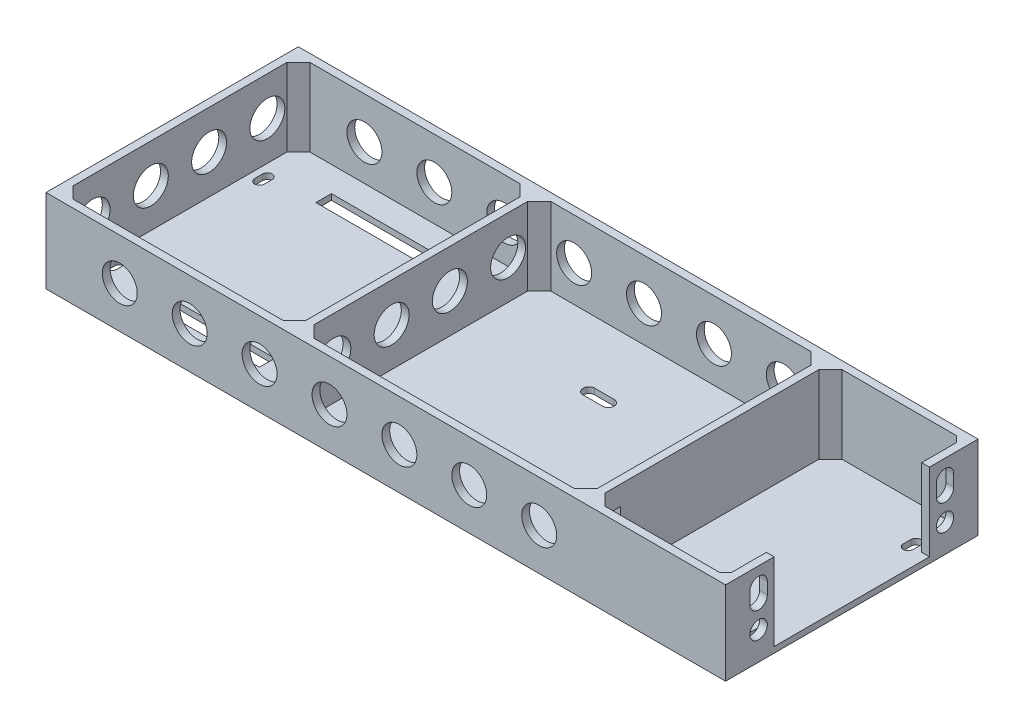
SolidWorks part; units mm, degrees
ref_plane "Спереди" through (0, 0, 0) normal (0, 0, 1) x (1, 0, 0)
ref_plane "Сверху" through (0, 0, 0) normal (0, 1, 0) x (1, 0, 0)
ref_plane "Справа" through (0, 0, 0) normal (1, 0, 0) x (0, 0, -1)
sketch "Эскиз1" plane through (0, 0, 0) normal (0, 1, 0) x (1, 0, 0)
  line L1 (-87.5, -32.5) -> (87.5, -32.5)
  line L2 (-87.5, -32.5) -> (-87.5, 32.5)
  line L3 (-87.5, 32.5) -> (87.5, 32.5)
  line L4 (87.5, -32.5) -> (87.5, 32.5)
  line L5 (-87.5, -32.5) -> (87.5, 32.5) construction
  line L6 (-87.5, 32.5) -> (87.5, -32.5) construction
  point P0 (0, 0)
  dimension "D1" = 175
  dimension "D2" = 65
extrude "Бобышка-Вытянуть1" add sketch "Эскиз1" along normal blind 1.5
sketch "Эскиз3" plane through (0, 1.5, 0) normal (0, 1, 0) x (1, 0, 0)
  line L5 (-87.5, -32.5) -> (87.5, -32.5)
  line L6 (-87.5, -32.5) -> (-87.5, 32.5)
  line L7 (-87.5, 32.5) -> (87.5, 32.5)
  line L8 (85.5, -30.5) -> (85.5, 30.5)
  line L9 (85.5, 30.5) -> (-85.5, 30.5)
  line L10 (-85.5, 30.5) -> (-85.5, -30.5)
  line L11 (-85.5, -30.5) -> (85.5, -30.5)
  line L12 (85.5, -30.5) -> (85.5, 30.5)
  line L13 (85.5, 30.5) -> (-85.5, 30.5)
  line L14 (-85.5, 30.5) -> (-85.5, -30.5)
  line L15 (-85.5, -30.5) -> (85.5, -30.5)
  line L16 (87.5, -32.5) -> (87.5, 32.5)
  line L17 (-87.5, -32.5) -> (87.5, 32.5) construction
  line L18 (-87.5, 32.5) -> (87.5, -32.5) construction
  point P0 (0, 0)
  dimension "D1" = 2
extrude "Бобышка-Вытянуть2" add sketch "Эскиз3" along normal blind 20
sketch "Эскиз4" plane through (87.5, 0, 0) normal (1, 0, 0) x (0, 0, -1)
  line L7 (-32.5, 21.5) -> (32.5, 21.5) construction
  line L8 (-20, 21.5) -> (20, 21.5)
  line L9 (-20, 21.5) -> (-20, 1.5)
  line L10 (-20, 1.5) -> (20, 1.5)
  line L11 (20, 21.5) -> (20, 1.5)
  line L12 (-32.5, 21.5) -> (-32.5, 0) construction
  dimension "D1" = 40
  dimension "D2" = 20
  dimension "D3" = 12.5
extrude "Вырез-Вытянуть1" cut sketch "Эскиз4" against normal blind 2
sketch "Эскиз5" plane through (0, 1.5, 0) normal (0, 1, 0) x (1, 0, 0)
  line L0 (57.5, 20) -> (57.5, 30.5)
  line L1 (87.5, 20) -> (57.5, 20)
  line L2 (87.5, 20) -> (87.5, -20)
  line L3 (87.5, -20) -> (57.5, -20)
  line L4 (57.5, 20) -> (57.5, -20)
  line L5 (85.5, 30.5) -> (-85.5, 30.5) construction
  line L6 (57.5, -20) -> (57.5, -30.5)
  line L7 (-85.5, -30.5) -> (85.5, -30.5) construction
  dimension "D1" = 30
  dimension "D2" = 40
sketch "Эскиз6" plane through (87.5, 0, 0) normal (1, 0, 0) x (0, 0, -1)
  line L0 (-32.5, 21.5) -> (-20, 21.5) construction
  line L1 (-20, 21.5) -> (-20, 1.5) construction
  line L2 (-24, 16.9184) -> (-24, 13.9184) construction
  line L3 (-21.75, 16.9184) -> (-21.75, 13.9184)
  line L4 (-26.25, 16.9184) -> (-26.25, 13.9184)
  circle A1 centre (-24, 7.25) radius 2.25
  arc A2 (-21.75, 16.9184) -> (-26.25, 16.9184) centre (-24, 16.9184) ccw
  arc A3 (-26.25, 13.9184) -> (-21.75, 13.9184) centre (-24, 13.9184) ccw
  point P8 (-24, 15.4184)
  dimension "D1" = 4.5
  dimension "D3" = 4.5
  dimension "D2" = 3
  dimension "D4" = 14.25
  dimension "D6" = 4
extrude "Вырез-Вытянуть2" cut sketch "Эскиз6" against normal blind 2
ref_plane "Плоскость2" through (0, 0, 0) normal (0, 0, -1) x (-1, 0, 0)
mirror "Зеркальное отражение2" about plane through (0, 0, 0) normal (0, 0, -1) of "Вырез-Вытянуть2"
sketch "Эскиз9" plane through (0, 1.5, 0) normal (0, 1, 0) x (1, 0, 0)
  line L0 (85.5, 20) -> (85.5, 30.5) construction
  line L1 (49.5, 30.5) -> (51.5, 30.5)
  line L2 (49.5, 30.5) -> (49.5, -30.5)
  line L3 (49.5, -30.5) -> (51.5, -30.5)
  line L4 (51.5, 30.5) -> (51.5, -30.5)
  line L5 (85.5, 30.5) -> (-85.5, 30.5) construction
  line L6 (-85.5, -30.5) -> (85.5, -30.5) construction
  dimension "D1" = 2
  dimension "D2" = 34
  dimension "D3" = 0
  dimension "D4" = 0
extrude "Бобышка-Вытянуть4" add sketch "Эскиз9" along normal blind 20
sketch "Эскиз12" plane through (51.5, 0, 0) normal (1, 0, 0) x (0, 0, -1)
  line L0 (-30.5, 21.5) -> (30.5, 21.5) construction
  line L1 (-27.5, 16.5) -> (-23.5, 16.5)
  line L2 (-27.5, 16.5) -> (-27.5, 6.5)
  line L3 (-27.5, 6.5) -> (-23.5, 6.5)
  line L4 (-23.5, 16.5) -> (-23.5, 6.5)
  line L5 (-30.5, 21.5) -> (-30.5, 1.5) construction
  dimension "D1" = 10
  dimension "D2" = 4
  dimension "D3" = 5
  dimension "D4" = 3
extrude "Вырез-Вытянуть4" cut sketch "Эскиз12" against normal blind 2
chamfer "Фаска1" distance 3 angle 45 4 edges at (-85.5, 11.5, -30.5) (49.5, 11.5, 30.5) (49.5, 11.5, -30.5) (-85.5, 11.5, 30.5)
chamfer "Фаска2" distance 3 angle 45 2 edges at (51.5, 11.5, -30.5) (51.5, 11.5, 30.5)
chamfer "Фаска3" distance 1.5 angle 45 2 edges at (85.5, 11.5, 30.5) (85.5, 11.5, -30.5)
sketch "Эскиз13" plane through (0, 0, -32.5) normal (0, 0, -1) x (-1, 0, 0)
  line L21 (-87.5, 10.75) -> (86.3564, 10.75) construction
  line L22 (-87.5, 21.5) -> (-87.5, 0) construction
  line L23 (-49.5, 16.5) -> (-49.5, 21.5) construction
  circle A0 centre (-39.5, 10.75) radius 4.5
  dimension "D2" = 9
  dimension "D1" = 10
extrude "Вырез-Вытянуть5" cut sketch "Эскиз13" against normal blind 71
ref_plane "Плоскость3" through (39.5, 0, 0) normal (-1, 0, 0) x (0, 0, 1)
pattern_linear "Линейный массив1" count 7 spacing 18 along (-1, 0, 0) of "Вырез-Вытянуть5"
sketch "Эскиз14" plane through (0, 1.5, 0) normal (0, 1, 0) x (1, 0, 0)
  line L0 (-85.5, 27.5) -> (-85.5, -27.5) construction
  line L1 (-25.5, 30.5) -> (-23.5, 30.5)
  line L2 (-25.5, 30.5) -> (-25.5, -30.5)
  line L3 (-25.5, -30.5) -> (-23.5, -30.5)
  line L4 (-23.5, 30.5) -> (-23.5, -30.5)
  line L5 (46.5, 30.5) -> (-82.5, 30.5) construction
  line L6 (-82.5, -30.5) -> (46.5, -30.5) construction
  point P6 (-24.5, 30.5)
  dimension "D1" = 60
  dimension "D2" = 0
  dimension "D3" = 0
  dimension "D4" = 2
extrude "Бобышка-Вытянуть5" add sketch "Эскиз14" along normal blind 20
chamfer "Фаска4" distance 3 angle 45 2 edges at (-25.5, 11.5, 30.5) (-25.5, 11.5, -30.5)
chamfer "Фаска5" distance 3 angle 45 2 edges at (-23.5, 11.5, 30.5) (-23.5, 11.5, -30.5)
sketch "Эскиз15" plane through (-23.5, 0, 0) normal (1, 0, 0) x (0, 0, -1)
  line L20 (-27.5, 11.5) -> (27.5, 11.5) construction
  line L33 (-27.5, 21.5) -> (-27.5, 1.5) construction
  line L34 (27.5, 1.5) -> (27.5, 21.5) construction
  circle A0 centre (-22.5, 11.5) radius 4.5
  dimension "D1" = 9
  dimension "D2" = 5
extrude "Вырез-Вытянуть6" cut sketch "Эскиз15" against normal blind 71
pattern_linear "Линейный массив2" count 4 spacing 15 along (0, 0, -1) of "Вырез-Вытянуть6"
sketch "Эскиз16" plane through (0, 1.5, 0) normal (0, 1, 0) x (1, 0, 0)
  line L3 (6.8, 13) -> (11.8, 13) construction
  line L4 (6.8, 14.5) -> (11.8, 14.5)
  line L5 (6.8, 11.5) -> (11.8, 11.5)
  line L7 (46.5, 30.5) -> (-20.5, 30.5) construction
  line L8 (39.5, 13) -> (44.5, 13) construction
  line L9 (39.5, 14.5) -> (44.5, 14.5)
  line L10 (39.5, 11.5) -> (44.5, 11.5)
  line L11 (49.5, 27.5) -> (49.5, -27.5) construction
  arc A2 (6.8, 14.5) -> (6.8, 11.5) centre (6.8, 13) ccw
  arc A3 (11.8, 11.5) -> (11.8, 14.5) centre (11.8, 13) ccw
  arc A4 (39.5, 14.5) -> (39.5, 11.5) centre (39.5, 13) ccw
  arc A5 (44.5, 11.5) -> (44.5, 14.5) centre (44.5, 13) ccw
  point P2 (9.3, 13)
  point P11 (42, 13)
  dimension "D1" = 5
  dimension "D2" = 3
  dimension "D3" = 16
  dimension "D4" = 16
  dimension "D5" = 5
  dimension "D6" = 5
  dimension "D7" = 32.7
extrude "Вырез-Вытянуть7" cut sketch "Эскиз16" against normal blind 4
sketch "Эскиз17" plane through (0, 1.5, 0) normal (0, 1, 0) x (1, 0, 0)
  line L1 (-21.4057, 21.2837) -> (3.5943, 21.2837)
  line L2 (-21.4057, 21.2837) -> (-21.4057, -18.7163)
  line L3 (-21.4057, -18.7163) -> (3.5943, -18.7163)
  line L4 (3.5943, 21.2837) -> (3.5943, -18.7163)
  dimension "D1" = 25
  dimension "D2" = 40
sketch "Эскиз18" plane through (0, 1.5, 0) normal (0, 1, 0) x (1, 0, 0)
  line L1 (-70.5, 24) -> (-43.5, 24)
  line L2 (-70.5, 24) -> (-70.5, 20)
  line L3 (-70.5, 20) -> (-43.5, 20)
  line L4 (-43.5, 24) -> (-43.5, 20)
  line L5 (-68.0533, -20) -> (-41.0533, -20)
  line L6 (-68.0533, -20) -> (-68.0533, -24)
  line L7 (-68.0533, -24) -> (-41.0533, -24)
  line L8 (-41.0533, -20) -> (-41.0533, -24)
  line L9 (-28.5, 30.5) -> (-82.5, 30.5) construction
  line L12 (-85.5, 27.5) -> (-85.5, -27.5) construction
  dimension "D1" = 40
  dimension "D2" = 6.5
  dimension "D3" = 4
  dimension "D4" = 4
  dimension "D5" = 15
  dimension "D6" = 27
extrude "Вырез-Вытянуть8" cut sketch "Эскиз18" against normal blind 5
sketch "Эскиз19" plane through (0, 1.5, 0) normal (0, 1, 0) x (1, 0, 0)
  line L0 (82.5, 21.5) -> (82.5, 19.5) construction
  line L1 (83.75, 21.5) -> (83.75, 19.5)
  line L2 (81.25, 21.5) -> (81.25, 19.5)
  line L3 (82.5, -18.5) -> (82.5, -20.5) construction
  line L4 (83.75, -18.5) -> (83.75, -20.5)
  line L5 (81.25, -18.5) -> (81.25, -20.5)
  line L6 (82.5, 30.5) -> (82.5, -30.5) construction
  line L7 (84, 30.5) -> (54.5, 30.5) construction
  line L8 (54.5, -30.5) -> (84, -30.5) construction
  line L9 (85.5, 20) -> (85.5, 29) construction
  line L10 (-82.5, 30.5) -> (-82.5, -30.5) construction
  line L11 (-28.5, 30.5) -> (-82.5, 30.5) construction
  line L12 (-82.5, -30.5) -> (-28.5, -30.5) construction
  line L13 (-85.5, 27.5) -> (-85.5, -27.5) construction
  line L15 (-82.5, 19.5) -> (-82.5, 17.5) construction
  line L16 (-81.25, 19.5) -> (-81.25, 17.5)
  line L17 (-83.75, 19.5) -> (-83.75, 17.5)
  line L18 (-82.5, -18.5) -> (-82.5, -20.5) construction
  line L19 (-81.25, -18.5) -> (-81.25, -20.5)
  line L20 (-83.75, -18.5) -> (-83.75, -20.5)
  arc A0 (83.75, 21.5) -> (81.25, 21.5) centre (82.5, 21.5) ccw
  arc A1 (81.25, 19.5) -> (83.75, 19.5) centre (82.5, 19.5) ccw
  arc A2 (83.75, -18.5) -> (81.25, -18.5) centre (82.5, -18.5) ccw
  arc A3 (81.25, -20.5) -> (83.75, -20.5) centre (82.5, -20.5) ccw
  arc A4 (-81.25, 19.5) -> (-83.75, 19.5) centre (-82.5, 19.5) ccw
  arc A5 (-83.75, 17.5) -> (-81.25, 17.5) centre (-82.5, 17.5) ccw
  arc A6 (-81.25, -18.5) -> (-83.75, -18.5) centre (-82.5, -18.5) ccw
  arc A7 (-83.75, -20.5) -> (-81.25, -20.5) centre (-82.5, -20.5) ccw
  point P2 (82.5, 20.5)
  point P9 (82.5, -19.5)
  point P22 (89.1382, 17.8711)
  point P23 (-75.807, 19.5)
  point P24 (0, 0)
  point P35 (-82.5, 18.5)
  point P42 (-82.5, -19.5)
  point P49 (-80.7592, 10.3542)
  dimension "D1" = 2
  dimension "D2" = 2.5
  dimension "D3" = 40
  dimension "D4" = 10
  dimension "D5" = 3
  dimension "D6" = 3
  dimension "D7" = 2.5
  dimension "D8" = 2
  dimension "D9" = 2
  dimension "D10" = 2.5
  dimension "D11" = 40
  dimension "D12" = 10
extrude "Вырез-Вытянуть9" cut sketch "Эскиз19" against normal blind 10
